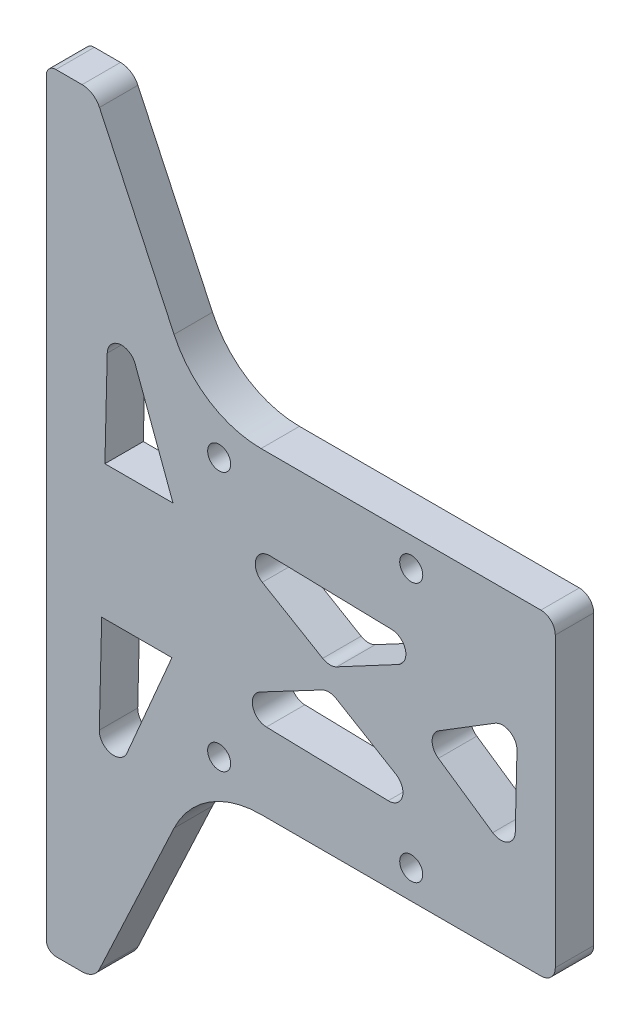
SolidWorks part; units mm, degrees
material "S-玻璃纤维"
ref_plane "前视基准面" through (0, 0, 0) normal (0, 0, 1) x (1, 0, 0)
ref_plane "上视基准面" through (0, 0, 0) normal (0, 1, 0) x (1, 0, 0)
ref_plane "右视基准面" through (0, 0, 0) normal (1, 0, 0) x (0, 0, -1)
other "Configuration Table"
sketch "草图1" plane through (0, 0, 0) normal (0, 0, 1) x (1, 0, 0)
  line L0 (46.7231, 42.8869) -> (40.8876, 39.2897)
  line L1 (48.8308, 34.1043) -> (49.0098, 41.5741)
  line L2 (3.7279, 78.9776) -> (1, 78.9776)
  line L3 (0, 77.9776) -> (0, -0.0224)
  line L4 (1, -1.0224) -> (3.7279, -1.0224)
  line L5 (5.5393, 0.1297) -> (13.3035, 16.717)
  line L6 (22.3605, 22.4776) -> (51.5, 22.4776)
  line L7 (53, 23.9776) -> (53, 53.9776)
  line L8 (51.5, 55.4776) -> (22.3605, 55.4776)
  line L9 (13.3035, 61.2382) -> (5.5393, 77.8255)
  line L10 (40.8273, 36.7751) -> (46.4839, 32.9025)
  line L11 (35.9752, 45.9678) -> (23.2929, 46.2716)
  line L12 (30.2497, 39.7339) -> (36.6451, 43.1447)
  line L13 (22.4939, 43.4806) -> (28.7808, 39.7661)
  line L14 (28.7116, 36.879) -> (22.2541, 33.4698)
  line L15 (36.4051, 33.1277) -> (30.1804, 36.8407)
  line L16 (22.9185, 30.6437) -> (35.6008, 30.3399)
  line L17 (8.399, 21.0367) -> (15.6936, 38.078)
  line L18 (6.3448, 56.0753) -> (5.5204, 21.6629)
  line L19 (15.7203, 39.1918) -> (9.2501, 56.5629)
  line L20 (0, 93.865) -> (0, -74.3176) construction
  arc A0 (1, 78.9776) -> (0, 77.9776) centre (1, 77.9776) ccw
  arc A1 (0, -0.0224) -> (1, -1.0224) centre (1, -0.0224) ccw
  arc A2 (3.7279, -1.0224) -> (5.5393, 0.1297) centre (3.7279, 0.9776) ccw
  arc A3 (22.3605, 22.4776) -> (13.3035, 16.717) centre (22.3605, 12.4776) ccw
  arc A4 (51.5, 22.4776) -> (53, 23.9776) centre (51.5, 23.9776) ccw
  arc A5 (53, 53.9776) -> (51.5, 55.4776) centre (51.5, 53.9776) ccw
  arc A6 (13.3035, 61.2382) -> (22.3605, 55.4776) centre (22.3605, 65.4776) ccw
  arc A7 (5.5393, 77.8255) -> (3.7279, 78.9776) centre (3.7279, 76.9776) ccw
  arc A8 (49.0098, 41.5741) -> (46.7231, 42.8869) centre (47.5102, 41.61) ccw
  arc A9 (46.4839, 32.9025) -> (48.8308, 34.1043) centre (47.3312, 34.1402) ccw
  arc A10 (40.1751, 38.0487) -> (40.8273, 36.7751) centre (41.6747, 38.0128) ccw
  arc A11 (40.8876, 39.2897) -> (40.1751, 38.0487) centre (41.6747, 38.0128) ccw
  arc A12 (36.6451, 43.1447) -> (35.9752, 45.9678) centre (35.9392, 44.4682) ccw
  arc A13 (28.7808, 39.7661) -> (30.2497, 39.7339) centre (29.5438, 41.0575) ccw
  arc A14 (21.7574, 44.808) -> (22.4939, 43.4806) centre (23.257, 44.772) ccw
  arc A15 (23.2929, 46.2716) -> (21.7574, 44.808) centre (23.257, 44.772) ccw
  arc A16 (30.1804, 36.8407) -> (28.7116, 36.879) centre (29.4119, 35.5525) ccw
  arc A17 (35.6008, 30.3399) -> (36.4051, 33.1277) centre (35.6367, 31.8394) ccw
  arc A18 (21.4549, 32.1792) -> (22.9185, 30.6437) centre (22.9544, 32.1433) ccw
  arc A19 (22.2541, 33.4698) -> (21.4549, 32.1792) centre (22.9544, 32.1433) ccw
  arc A20 (5.5204, 21.6629) -> (8.399, 21.0367) centre (7.02, 21.6269) ccw
  arc A21 (9.2501, 56.5629) -> (6.3448, 56.0753) centre (7.8444, 56.0393) ccw
  arc A22 (15.6936, 38.078) -> (15.7203, 39.1918) centre (14.3147, 38.6683) ccw
extrude "凸台-拉伸1" add sketch "草图1" along normal blind 11
sketch "草图2" plane through (0, 0, 11) normal (0, 0, 1) x (1, 0, 0)
  line L5 (53, 23.9776) -> (53, 53.9776) construction
  line L6 (22.3605, 22.4776) -> (51.5, 22.4776) construction
  line L8 (23, 22.4776) -> (23, 27.4776)
  line L9 (23, 27.4776) -> (53, 27.4776)
  line L11 (53, 38.9776) -> (-37.4568, 38.9776) construction
  line L13 (23, 50.4776) -> (53, 50.4776)
  line L14 (23, 55.4776) -> (23, 50.4776)
  line L24 (3.7279, 78.9776) -> (1, 78.9776)
  line L25 (0, 77.9776) -> (0, -0.0224)
  line L26 (1, -1.0224) -> (3.7279, -1.0224)
  line L27 (5.5393, 0.1297) -> (13.3035, 16.717)
  line L28 (22.3605, 22.4776) -> (51.5, 22.4776)
  line L29 (53, 23.9776) -> (53, 53.9776)
  line L30 (51.5, 55.4776) -> (22.3605, 55.4776)
  line L31 (13.3035, 61.2382) -> (5.5393, 77.8255)
  line L32 (3.7279, 78.9776) -> (1, 78.9776)
  line L33 (0, 77.9776) -> (0, -0.0224)
  line L34 (1, -1.0224) -> (3.7279, -1.0224)
  line L35 (5.5393, 0.1297) -> (13.3035, 16.717)
  line L36 (22.3605, 22.4776) -> (23, 22.4776)
  line L37 (53, 27.4776) -> (53, 50.4776)
  line L38 (23, 55.4776) -> (22.3605, 55.4776)
  line L39 (13.3035, 61.2382) -> (5.5393, 77.8255)
  arc A8 (5.5393, 77.8255) -> (3.7279, 78.9776) centre (3.7279, 76.9776) ccw
  arc A9 (1, 78.9776) -> (0, 77.9776) centre (1, 77.9776) ccw
  arc A10 (0, -0.0224) -> (1, -1.0224) centre (1, -0.0224) ccw
  arc A11 (3.7279, -1.0224) -> (5.5393, 0.1297) centre (3.7279, 0.9776) ccw
  arc A12 (22.3605, 22.4776) -> (13.3035, 16.717) centre (22.3605, 12.4776) ccw
  arc A13 (51.5, 22.4776) -> (53, 23.9776) centre (51.5, 23.9776) ccw
  arc A14 (53, 53.9776) -> (51.5, 55.4776) centre (51.5, 53.9776) ccw
  arc A15 (13.3035, 61.2382) -> (22.3605, 55.4776) centre (22.3605, 65.4776) ccw
  arc A16 (5.5393, 77.8255) -> (3.7279, 78.9776) centre (3.7279, 76.9776) ccw
  arc A17 (1, 78.9776) -> (0, 77.9776) centre (1, 77.9776) ccw
  arc A18 (0, -0.0224) -> (1, -1.0224) centre (1, -0.0224) ccw
  arc A19 (3.7279, -1.0224) -> (5.5393, 0.1297) centre (3.7279, 0.9776) ccw
  arc A20 (22.3605, 22.4776) -> (13.3035, 16.717) centre (22.3605, 12.4776) ccw
  arc A23 (13.3035, 61.2382) -> (22.3605, 55.4776) centre (22.3605, 65.4776) ccw
  dimension "D3" = 0
extrude "切除-拉伸1" cut sketch "草图2" against normal blind 7
sketch "草图3" plane through (0, 55.4776, 0) normal (0, 1, 0) x (1, 0, 0)
  line L0 (53, -11) -> (53, 0) construction
  line L1 (51.5, 0) -> (22.3605, 0) construction
  circle A0 centre (48, -8) radius 2.05
  circle A1 centre (28, -8) radius 2.05
  dimension "D1" = 4.1
  dimension "D2" = 5
  dimension "D4" = 8
  dimension "D3" = 2
extrude "切除-拉伸2" cut sketch "草图3" against normal blind 37
fillet "圆角1" radius 2 6 edges at (53, 27.4776, 7.5) (23, 27.4776, 7.5) (23, 22.4776, 7.5) (23, 50.4776, 7.5) (53, 50.4776, 7.5) (23, 55.4776, 7.5)
sketch "草图4" plane through (0, 0, 4) normal (0, 0, 1) x (1, 0, 0)
  line L0 (0, 38.9776) -> (68.8704, 38.9776) construction
  line L1 (0, 77.9776) -> (0, -0.0224) construction
  line L2 (16.1183, 31.9776) -> (3.8985, 31.9776)
  line L3 (16.1183, 38.9776) -> (3.8985, 38.9776)
  line L4 (16.1183, 31.9776) -> (16.1183, 45.9776)
  line L5 (16.1183, 45.9776) -> (3.8985, 45.9776)
  line L6 (3.8985, 31.9776) -> (3.8985, 45.9776)
  line M21 (15.6936, 38.078) -> (8.399, 21.0367)
  line M23 (5.5204, 21.6629) -> (6.3448, 56.0753)
  line M25 (9.2501, 56.5629) -> (15.7203, 39.1918)
  arc M26 (15.7203, 39.1918) -> (15.6936, 38.078) centre (14.3147, 38.6683) cw
  dimension "D1" = 7
extrude "凸台-拉伸2" add sketch "草图4" against normal blind 4 contours L5 L3 M25 M23 M26 | L3 L2 M26 M23 M21 region at (10.2503, 35.6621, 4) region at (10.2909, 42.2867, 4)
sketch "草图5" plane through (0, 55.4776, 0) normal (0, 1, 0) x (1, 0, 0)
  line L0 (23, -4) -> (25, -4) construction
  line L1 (23, -4) -> (57.4615, -4)
  line L2 (23, -4) -> (23, -12.3457)
  line L3 (23, -12.3457) -> (57.4615, -12.3457)
  line L4 (57.4615, -4) -> (57.4615, -12.3457)
  line L5 (25, -4) -> (22.3605, -4) construction
extrude "切除-拉伸3" cut sketch "草图5" against normal blind 34
sketch "草图6" plane through (0, 0, 4) normal (0, 0, 1) x (1, 0, 0)
  line L0 (53, 23.9776) -> (53, 53.9776) construction
  line L1 (0, 38.9776) -> (83.1383, 38.9776) construction
  line L2 (0, 77.9776) -> (0, -0.0224) construction
  line L3 (51.5, 55.4776) -> (22.3605, 55.4776) construction
  circle A0 centre (38, 52.4776) radius 1.2
  circle A1 centre (18, 52.4776) radius 1.2
  circle A2 centre (18, 25.4776) radius 1.2
  circle A3 centre (38, 25.4776) radius 1.2
  dimension "D1" = 2.4
  dimension "D2" = 15
  dimension "D4" = 3
  dimension "D3" = 2
extrude "切除-拉伸4" cut sketch "草图6" against normal blind 10
